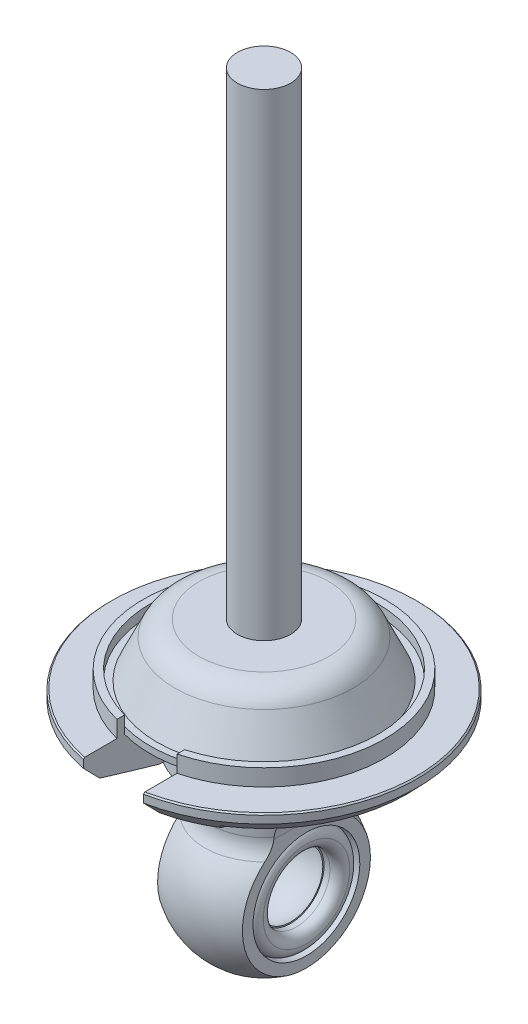
SolidWorks part; units mm, degrees
ref_plane "Front Plane" through (0, 0, 0) normal (0, 0, 1) x (1, 0, 0)
ref_plane "Top Plane" through (0, 0, 0) normal (0, 1, 0) x (1, 0, 0)
ref_plane "Right Plane" through (0, 0, 0) normal (1, 0, 0) x (0, 0, -1)
sketch "Sketch1" plane through (0, 0, 0) normal (1, 0, 0) x (0, 0, -1)
  line L0 (0, 0) -> (0, -276.2324) construction
  line L1 (0, -95.63) -> (3.99, -95.63)
  line L2 (3.99, -95.63) -> (3.99, -167.13)
  line L3 (3.99, -167.13) -> (9.7213, -167.13)
  line L4 (13.3465, -169.4395) -> (16, -175.13)
  line L5 (16, -175.13) -> (17, -175.13)
  line L6 (17, -175.13) -> (17, -173.63)
  line L7 (17, -173.63) -> (18.1, -173.63)
  line L8 (18.1, -173.63) -> (18.1, -176.13)
  line L9 (18.1, -176.13) -> (22.8, -176.13)
  line L10 (23, -176.33) -> (23, -177.48)
  line L11 (23, -177.48) -> (20.61, -179.97)
  line L12 (20.61, -179.97) -> (12, -182.63)
  line L13 (12, -182.63) -> (10.95, -182.63)
  line L14 (10.95, -182.63) -> (10.95, -184)
  line L15 (10.95, -184) -> (10.6946, -184.23)
  line L16 (10.6946, -184.23) -> (8, -184.23) construction
  line L17 (8, -187.2144) -> (8, -189.8193)
  line L18 (22.8, -176.13) -> (23, -176.33)
  line L19 (8, -184.23) -> (8, -187.2144) construction
  line L21 (0, -211.13) -> (0, -95.63)
  arc A0 (0, -211.13) -> (8.9032, -192.3511) centre (0, -199.63) ccw
  arc A1 (9.7213, -167.13) -> (13.3465, -169.4395) centre (9.7213, -171.13) cw
  arc A2 (0, -188.13) -> (0, -211.13) centre (0, -199.63) ccw construction
  arc A3 (8, -191.3686) -> (0, -188.13) centre (0, -199.63) ccw construction
  arc A4 (8, -189.8193) -> (8.9032, -192.3511) centre (12, -189.8193) ccw
  arc A6 (10.6946, -184.23) -> (8, -187.2144) centre (11, -187.2144) ccw
  point P16 (23, -176.13)
  dimension "D2" = 23
  dimension "D23" = 4
  dimension "D24" = 4
  dimension "D25" = 3
  dimension "D1" = 199.63
  dimension "D3" = 16
  dimension "D4" = 15.4
  dimension "D5" = 0.23
  dimension "D6" = 21.9
  dimension "D7" = 42
  dimension "D8" = 17
  dimension "D9" = 12
  dimension "D10" = 20.61
  dimension "D11" = 19.66
  dimension "D12" = 22.15
  dimension "D13" = 23
  dimension "D14" = 23.5
  dimension "D15" = 18.1
  dimension "D16" = 26
  dimension "D17" = 1.1
  dimension "D18" = 24.5
  dimension "D19" = 16
  dimension "D20" = 32.5
  dimension "D21" = 65
  dimension "D22" = 3.99
  dimension "D26" = 104
revolve "Revolve1" add sketch "Sketch1" angle 360 about L0
sketch "Sketch2" plane through (0, 0, 0) normal (0, 0, 1) x (1, 0, 0)
  line L0 (0, 0) -> (0, -233.0262) construction
  line L1 (6.35, -209.2179) -> (6.35, -190.13)
  line L2 (22.5, -179.23) -> (22.5, -214.63)
  line L3 (9.35, -184.9338) -> (9.35, -182.63)
  line L4 (9.35, -182.63) -> (11, -182.63)
  line L5 (11, -182.63) -> (11, -180.03)
  line L6 (11.8, -179.23) -> (22.5, -179.23)
  line L7 (22.5, -214.63) -> (6.35, -214.63)
  line L8 (6.35, -214.63) -> (6.35, -209.2179)
  line L9 (-6.35, -214.63) -> (-6.35, -209.2179)
  line L10 (-22.5, -214.63) -> (-6.35, -214.63)
  line L11 (-11.8, -179.23) -> (-22.5, -179.23)
  line L12 (-11, -182.63) -> (-11, -180.03)
  line L13 (-9.35, -182.63) -> (-11, -182.63)
  line L14 (-9.35, -184.9338) -> (-9.35, -182.63)
  line L15 (-22.5, -179.23) -> (-22.5, -214.63)
  line L16 (-6.35, -209.2179) -> (-6.35, -190.13)
  arc A0 (-6.35, -209.2179) -> (6.35, -209.2179) centre (0, -199.63) ccw construction
  arc A1 (11, -180.03) -> (11.8, -179.23) centre (11.8, -180.03) cw
  arc A2 (6.35, -190.13) -> (9.35, -184.9338) centre (12.35, -190.13) cw
  arc A3 (-6.35, -190.13) -> (-9.35, -184.9338) centre (-12.35, -190.13) ccw
  arc A4 (-11, -180.03) -> (-11.8, -179.23) centre (-11.8, -180.03) ccw
  dimension "D2" = 23
  dimension "D4" = 6
  dimension "D12" = 0.8
  dimension "D1" = 199.63
  dimension "D3" = 12.7
  dimension "D5" = 9.5
  dimension "D6" = 18.7
  dimension "D7" = 17
  dimension "D8" = 11
  dimension "D9" = 20.4
  dimension "D10" = 45
  dimension "D11" = 15
extrude "Cut-Extrude6" cut sketch "Sketch2" against normal through all both and the other way through all
sketch "Sketch3" plane through (0, -182.63, 0) normal (0, -1, 0) x (1, 0, 0)
  line L0 (0, 0) -> (0, 28.2841) construction
  line L1 (4.5, 9.9826) -> (4.5, 28.2841)
  line L2 (4.5, 28.2841) -> (-4.5, 28.2841)
  line L3 (-4.5, 9.9826) -> (-4.5, 28.2841)
  arc A0 (9.35, 5.6991) -> (-9.35, 5.6991) centre (0, 0) ccw construction
  arc A1 (4.5, 9.9826) -> (-4.5, 9.9826) centre (0, 0) ccw
  dimension "D1" = 28.2841
  dimension "D2" = 9
extrude "Cut-Extrude7" cut sketch "Sketch3" against normal up to surface (6.5 mm away) up to face at (0, -176.13, 18.1)
sketch "Sketch4" plane through (0, -176.13, 0) normal (0, 1, 0) x (1, 0, 0)
  line L0 (0, 0) -> (0, -26.451) construction
  line L1 (-4.5, -16.3936) -> (-4.5, -17.5317)
  line L2 (4.5, -16.3936) -> (4.5, -17.5317)
  circle A0 centre (0, 0) radius 17 construction
  circle A1 centre (0, 0) radius 18.1 construction
  arc A2 (-4.5, -16.3936) -> (4.5, -16.3936) centre (0, 0) ccw
  arc A3 (-4.5, -17.5317) -> (4.5, -17.5317) centre (0, 0) ccw
  dimension "D1" = 9
extrude "Cut-Extrude8" cut sketch "Sketch4" along normal up to surface (2.5 mm away) up to face at (0, -173.63, 17)
sketch "Sketch5" plane through (6.35, 0, 0) normal (1, 0, 0) x (0, 0, -1)
  circle A0 centre (0, -199.63) radius 8
  arc A1 (-6.2406, -192.3511) -> (6.2406, -192.3511) centre (0, -199.63) ccw construction
  dimension "D1" = 16
extrude "Cut-Extrude9" cut sketch "Sketch5" against normal through all
sketch "Sketch6" plane through (0, 0, 0) normal (1, 0, 0) x (0, 0, -1)
  circle A0 centre (0, -199.63) radius 8 construction
  circle A1 centre (0, -199.63) radius 8
extrude "Boss-Extrude1" add sketch "Sketch6" along normal mid plane 8
sketch "Sketch7" plane through (4, 0, 0) normal (1, 0, 0) x (0, 0, -1)
  circle A0 centre (0, -199.63) radius 7.95
  circle A1 centre (0, -199.63) radius 4.99
  dimension "D1" = 15.9
  dimension "D2" = 9.98
extrude "Boss-Extrude2" add sketch "Sketch7" along normal blind 2.35
fillet "Fillet1" radius 1.47 2 edges at (6.35, -199.63, -4.99) (6.35, -199.63, -7.95)
mirror "Mirror1" about plane through (0, 0, 0) normal (1, 0, 0) of "Fillet1", "Boss-Extrude2"
sketch "Sketch8" plane through (0, 0, 0) normal (1, 0, 0) x (0, 0, -1)
  line L0 (0, -211.13) -> (0, -182.63) construction
  line L1 (4.7958, -182.63) -> (-4.7958, -182.63) construction
  line L2 (0, -193.38) -> (0, -205.88)
  arc A0 (-8.9032, -192.3511) -> (8.9032, -192.3511) centre (0, -199.63) ccw construction
  arc A1 (0, -205.88) -> (0, -193.38) centre (0, -199.63) ccw
  dimension "D1" = 12.5
revolve "Cut-Revolve1" cut sketch "Sketch8" angle 360 about L0
